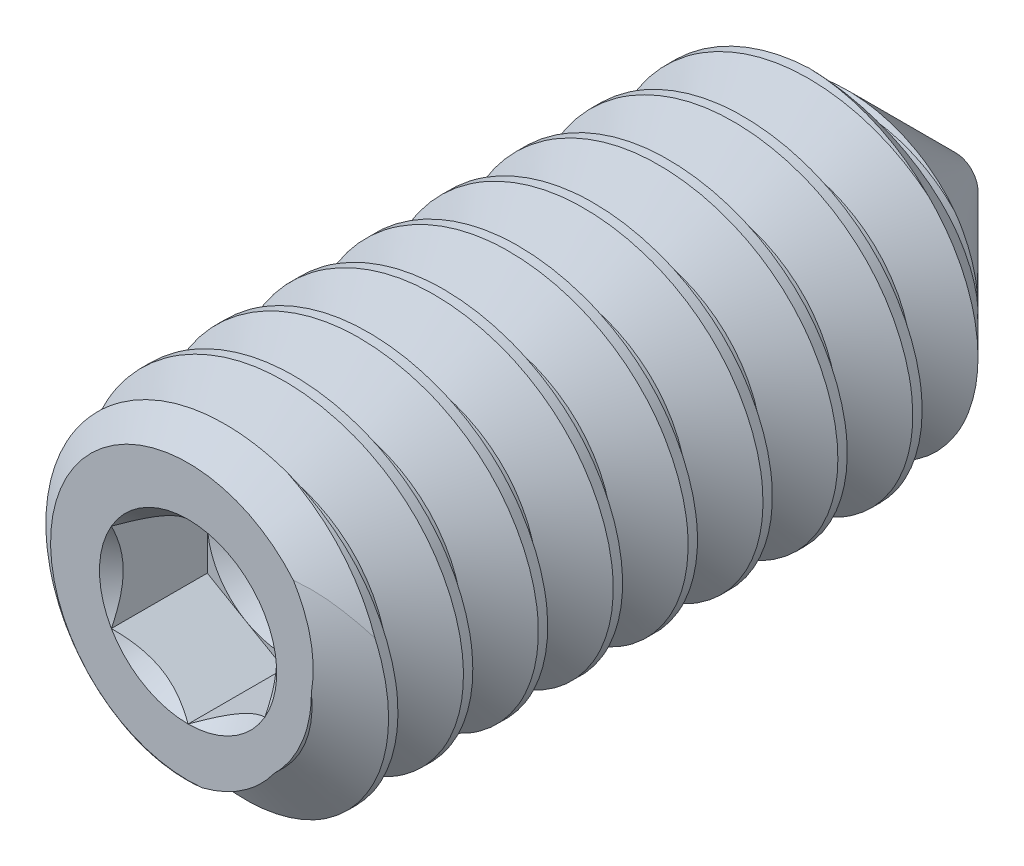
SolidWorks part; units mm, degrees
ref_plane "Front" through (0, 0, 0) normal (0, 0, 1) x (1, 0, 0)
ref_plane "Top" through (0, 0, 0) normal (0, 1, 0) x (1, 0, 0)
ref_plane "Right" through (0, 0, 0) normal (1, 0, 0) x (0, 0, -1)
sketch "Sketch22" plane through (0, 0, 0) normal (1, 0, 0) x (0, 0, -1)
  line L0 (-3.175, 0) -> (-3.175, 1.1379)
  line L1 (-3.175, 1.1379) -> (-2.9758, 1.4224)
  line L2 (-2.9758, 1.4224) -> (1.9375, 1.4224)
  line L3 (1.9375, 1.4224) -> (3.175, 0.1849)
  line L4 (-3.175, 1.1379) -> (-3.175, -1.1379) construction
  line L5 (3.175, 0) -> (-3.175, 0)
  line L6 (0, 1.4224) -> (0, -1.4224) construction
  line L8 (3.175, 0.1849) -> (3.175, 0)
  line L9 (-3.175, -1.4224) -> (3.175, -1.4224) construction
  line L10 (3.175, 0.1849) -> (3.175, -0.1849) construction
  line L11 (3.175, -0.1849) -> (1.9375, -1.4224) construction
  line L13 (3.175, 0.1849) -> (2.9901, 0) construction
  line L15 (2.9901, 0) -> (3.175, -0.1849) construction
  dimension "D3" = 35
  dimension "D7" = 2.2758
  dimension "Dia" = 2.8448
  dimension "Length" = 6.35
  dimension "D2" = 0.3698
  dimension "D1" = 90
  dimension "D4" = 90
revolve "Revolve1" add sketch "Sketch22" angle 360 about L5
ref_plane "Plane1" through (0, 0, -3.175) normal (0, 0, 1) x (1, 0, 0)
sketch "Sketch27" plane through (0, 0, -3.175) normal (0, 0, 1) x (1, 0, 0)
  circle A0 centre (0, 0) radius 1.4224 construction
  circle A1 centre (0, 0) radius 1.4224
curve "Helix/Spiral1" pitch 0.6195 height 6.9695 radius 1.4224 centre (0, 0, -3.175) axis (0, 0, 1) start towards (0, 1, 0)
sketch "Sketch28" plane through (0, 0, 0) normal (1, 0, 0) x (0, 0, -1)
  line L0 (3.175, 1.4224) -> (3.7171, 1.4224)
  line L1 (3.7171, 1.4224) -> (3.4848, 1.02)
  line L2 (3.4848, 1.02) -> (3.4073, 1.02)
  line L3 (3.4073, 1.02) -> (3.175, 1.4224)
  line L4 (3.2912, 1.2212) -> (3.6009, 1.2212) construction
  line L6 (-2.9758, 1.4224) -> (1.9375, 1.4224) construction
  line L7 (3.175, 1.6085) -> (3.175, -1.6085) construction
  dimension "D1" = 0.0774
  dimension "D3" = 60
  dimension "D2" = 0.3098
sweep "Cut-Sweep2" cut profiles "Sketch28" path "Helix/Spiral1" align with end faces yes
sketch "Sketch23" plane through (0, 0, 3.175) normal (0, 0, 1) x (1, 0, 0)
  line L1 (0, 0.7332) -> (-0.635, 0.3666)
  line L2 (-0.635, 0.3666) -> (-0.635, -0.3666)
  line L3 (-0.635, -0.3666) -> (0, -0.7332)
  line L4 (0, -0.7332) -> (0.635, -0.3666)
  line L5 (0.635, -0.3666) -> (0.635, 0.3666)
  line L6 (0.635, 0.3666) -> (0, 0.7332)
  circle A0 centre (0, 0) radius 0.635 construction
  dimension "Hex" = 1.27
extrude "Cut-Extrude10" cut sketch "Sketch23" against normal blind 0.7937
sketch "Sketch24" plane through (0, 0, 3.175) normal (0, 0, 1) x (1, 0, 0)
  circle A0 centre (0, 0) radius 0.7332
extrude "Cut-Extrude11" cut sketch "Sketch24" against normal through all draft 45
sketch "Sketch26" plane through (0, 0, 2.3812) normal (0, 0, 1) x (1, 0, 0)
  circle A0 centre (0, 0) radius 0.635 construction
  circle A1 centre (0, 0) radius 0.635
extrude "Cut-Extrude12" cut sketch "Sketch26" against normal through all draft 60
sketch "Sketch30" plane through (0, 0, 0) normal (1, 0, 0) x (0, 0, -1)
  line L0 (-2.9758, 1.4224) -> (1.9375, 1.4224) construction
  line L1 (-3.175, 0) -> (-3.175, 1.1379) construction
  line L3 (-3.175, -1.4224) -> (3.175, -1.4224) construction
  point P0 (-3.175, 1.4224)
  point P1 (1.9375, 1.4224)
  point P2 (1.9375, -1.4224)
  point P11 (1.0082, -1.4224)
  dimension "D1" = 0.9293
equation "\"D7@Sketch22\"=\"Dia@Sketch22\"*.8"
equation "\"D1@Sketch28\" = \"D4@Helix/Spiral1\" * .125"
equation "\"D3@Helix/Spiral1\" = \"Length@Sketch22\" + \"D4@Helix/Spiral1\""
equation "\"D1@Sketch30\" = \"D4@Helix/Spiral1\" * 1.5"
equation "\"hex Depth@Cut-Extrude10\" = \"Hex@Sketch23\" * .625"
equation "\"D2@Sketch28\" = \"D4@Helix/Spiral1\" * .5"
equation "\"D2@Sketch22\" = \"Dia@Sketch22\" * .13"
equation "\"D4@Sketch22\" = \"D1@Sketch22\""
